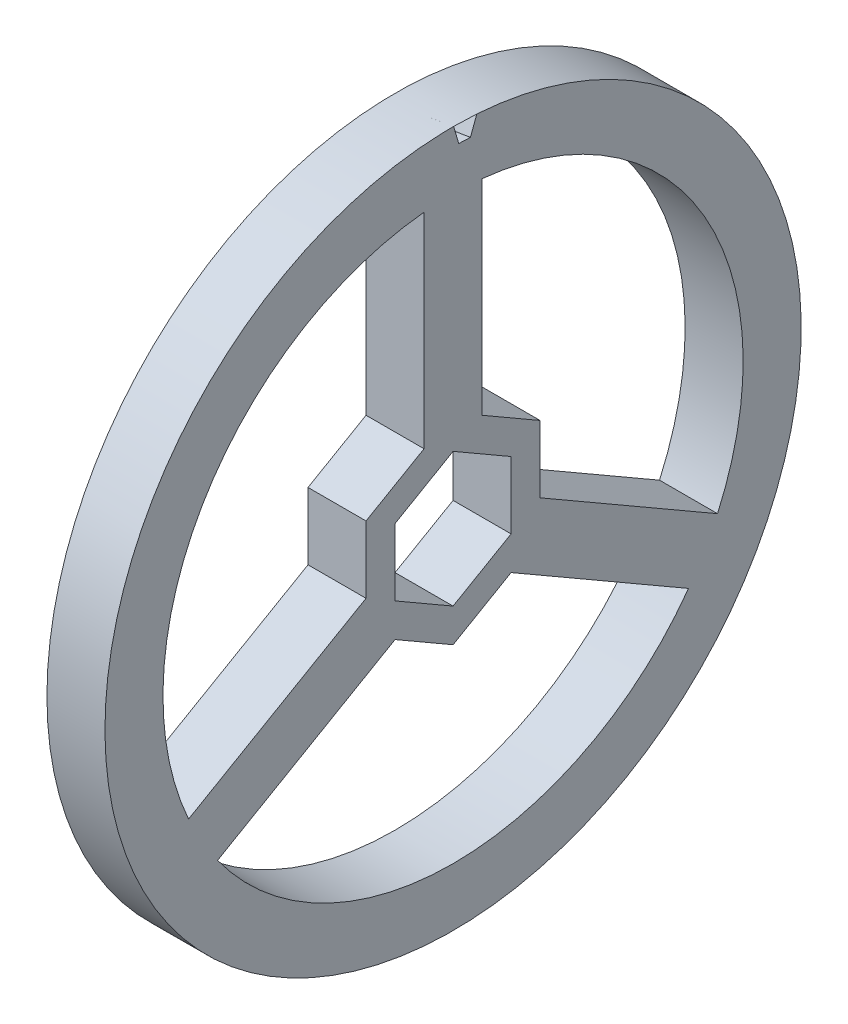
SolidWorks part; units mm, degrees
ref_plane "Front Plane" through (0, 0, 0) normal (0, 0, 1) x (1, 0, 0)
ref_plane "Top Plane" through (0, 0, 0) normal (0, 1, 0) x (1, 0, 0)
ref_plane "Right Plane" through (0, 0, 0) normal (1, 0, 0) x (0, 0, -1)
sketch "Sketch1" plane through (0, 0, 0) normal (1, 0, 0) x (0, 0, -1)
  line L0 (0, 0) -> (0, 30) construction
  line L1 (-2.5, 0) -> (-2.5, 30)
  line L2 (2.5, 0) -> (2.5, 30)
  line L3 (-1.25, -2.1651) -> (24.7308, -17.1651)
  line L4 (1.25, 2.1651) -> (27.2308, -12.8349)
  line L5 (0, 0) -> (25.9808, -15) construction
  line L6 (-1.25, 2.1651) -> (-27.2308, -12.8349)
  line L7 (1.25, -2.1651) -> (-24.7308, -17.1651)
  line L8 (0, 0) -> (-25.9808, -15) construction
  line L9 (7.5, 4.3301) -> (0, 8.6603)
  line L10 (0, 5.7735) -> (-5, 2.8868)
  line L11 (-5, 2.8868) -> (-5, -2.8868)
  line L12 (-5, -2.8868) -> (0, -5.7735)
  line L13 (0, -5.7735) -> (5, -2.8868)
  line L14 (5, -2.8868) -> (5, 2.8868)
  line L15 (5, 2.8868) -> (0, 5.7735)
  line L16 (0, 8.6603) -> (-7.5, 4.3301)
  line L17 (-7.5, 4.3301) -> (-7.5, -4.3301)
  line L18 (-7.5, -4.3301) -> (0, -8.6603)
  line L19 (0, -8.6603) -> (7.5, -4.3301)
  line L20 (7.5, -4.3301) -> (7.5, 4.3301)
  circle A0 centre (0, 0) radius 30
  arc A1 (-2.5, 0) -> (2.5, 0) centre (0, 0) ccw
  arc A2 (2.5, 30) -> (-2.5, 30) centre (0, 30) ccw
  circle A3 centre (0, 0) radius 25
  arc A4 (1.25, 2.1651) -> (-1.25, -2.1651) centre (0, 0) ccw
  arc A5 (24.7308, -17.1651) -> (27.2308, -12.8349) centre (25.9808, -15) ccw
  arc A6 (1.25, -2.1651) -> (-1.25, 2.1651) centre (0, 0) ccw
  arc A7 (-27.2308, -12.8349) -> (-24.7308, -17.1651) centre (-25.9808, -15) ccw
  circle A8 centre (0, 0) radius 5 construction
  point P3 (0, 15)
  point P11 (12.9904, -7.5)
  point P19 (-12.9904, -7.5)
  point P25 (0, 0)
  dimension "D1" = 60
  dimension "D3" = 2.5
  dimension "D4" = 5
  dimension "D6" = 10
  dimension "D2" = 30
  dimension "D7" = 2.5
  dimension "D5" = 3
extrude "Boss-Extrude1" add sketch "Sketch1" along normal blind 5 contours A3 L4 A0 L2 | A3 L1 A0 L6 | A3 L2 A0 L1 | A3 L3 A0 L4 | A3 L7 A0 L3 | A3 L6 A0 L7 | L3 A3 L4 L20 L19 | L6 A3 L7 L18 L17 | L2 A3 L1 L16 L9 | L16 L17 L6 L11 L10 L1 | L9 L16 L1 L10 L15 L2 | L4 L20 L9 L2 L15 L14 | L19 L20 L4 L14 L13 L3 | L18 L19 L3 L13 L12 L7 | L17 L18 L7 L12 L11 L6 region at (0, 3.1273, 5.4167) region at (0, 6.4952, 0) region at (0, -3.2476, 5.625) region at (0, 16.4434, 0) region at (0, -8.2217, 14.2404) region at (0, -3.2476, -5.625) region at (0, -6.2546, 0) region at (0, 12.7539, 22.0903) region at (0, 27.4617, 0) region at (0, 3.1273, -5.4167) region at (0, -13.7309, 23.7825) region at (0, -8.2217, -14.2404) region at (0, 27.3852, -3.0077) region at (0, -25.5163, 0) region at (0, -13.7309, -23.7825)
sketch "Sketch4" plane through (0, 0, 0) normal (-1, 0, 0) x (0, 0, 1)
  line L0 (-1, 29.9833) -> (-0.5, 28.4957)
  line L1 (0, 0) -> (0, 39.4734) construction
  line L2 (0.5, 28.4957) -> (1, 29.9833)
  arc A0 (1, 29.9833) -> (-1, 29.9833) centre (0, 0) ccw
  arc A1 (0.5, 28.4957) -> (-0.5, 28.4957) centre (0, 0) ccw
  circle A2 centre (0, 0) radius 30 construction
  dimension "D2" = 1
  dimension "D3" = 1
  dimension "D4" = 1
  dimension "D5" = 1.4877
sketch "Sketch5" plane through (5, 0, 0) normal (1, 0, 0) x (0, 0, -1)
  line L0 (0, 0) -> (1.3899, 39.8014) construction
  line L1 (0, 0) -> (0, 39.4734) construction
  line L2 (0.047, 30) -> (0.4948, 28.4957)
  line L3 (2.0458, 29.9302) -> (1.4942, 28.4608)
  arc A0 (2.0458, 29.9302) -> (0.047, 30) centre (0, 0) ccw
  arc A1 (1.4942, 28.4608) -> (0.4948, 28.4957) centre (0, 0) ccw
  dimension "D2" = 1.5
  dimension "D3" = 60
  dimension "D1" = 2
  dimension "D4" = 0.5
  dimension "D5" = 0.5
  dimension "D6" = 1
loft "Cut-Loft1" cut profiles "Sketch5", "Sketch4" connector at (5, 30, -0.047) connector at (0, 29.9833, 1)
